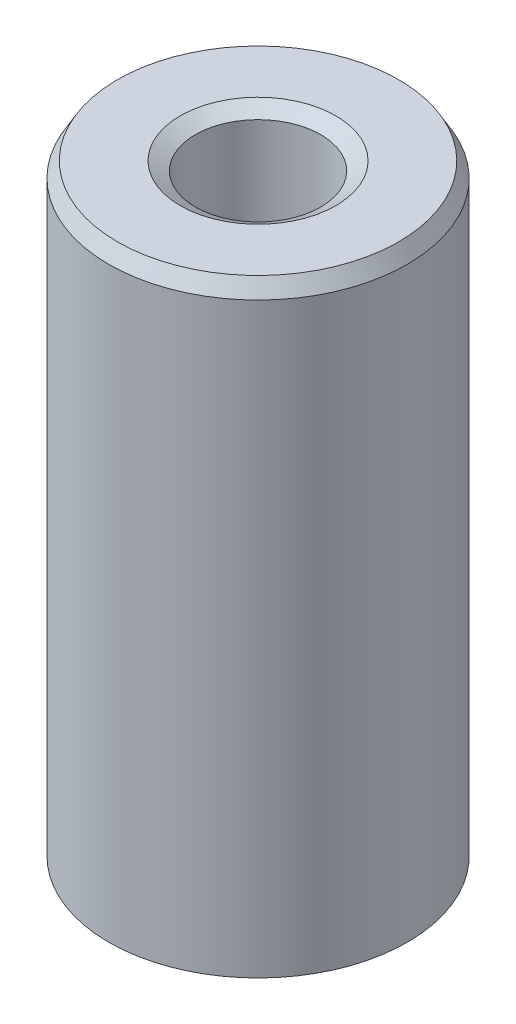
SolidWorks part; units mm, degrees
ref_plane "Front Plane" through (0, 0, 0) normal (0, 0, 1) x (1, 0, 0)
ref_plane "Top Plane" through (0, 0, 0) normal (0, 1, 0) x (1, 0, 0)
ref_plane "Right Plane" through (0, 0, 0) normal (1, 0, 0) x (0, 0, -1)
sketch "Sketch1" plane through (0, 0, 0) normal (0, 1, 0) x (1, 0, 0)
  circle A0 centre (0, 0) radius 37.5
  dimension "SLEEVE_OD" = 75
extrude "Boss-Extrude1" add sketch "Sketch1" along normal blind 153.4857
sketch "Sketch2" plane through (0, 0, 0) normal (0, 1, 0) x (1, 0, 0)
  circle A0 centre (0, 0) radius 15.7557
  dimension "BORE_D" = 31.5114
extrude "Cut-Extrude1" cut sketch "Sketch2" along normal through all
chamfer "Chamfer1" distance 3.797 angle 30 4 edges at (0, 153.4857, 15.7557) (0, 0, 15.7557) (0, 0, 37.5) (0, 153.4857, 37.5) first distance on face at (0, 153.4857, 15.7557) first distance on face at (0, 0, 15.7557) first distance on face at (0, 153.4857, 37.5)
